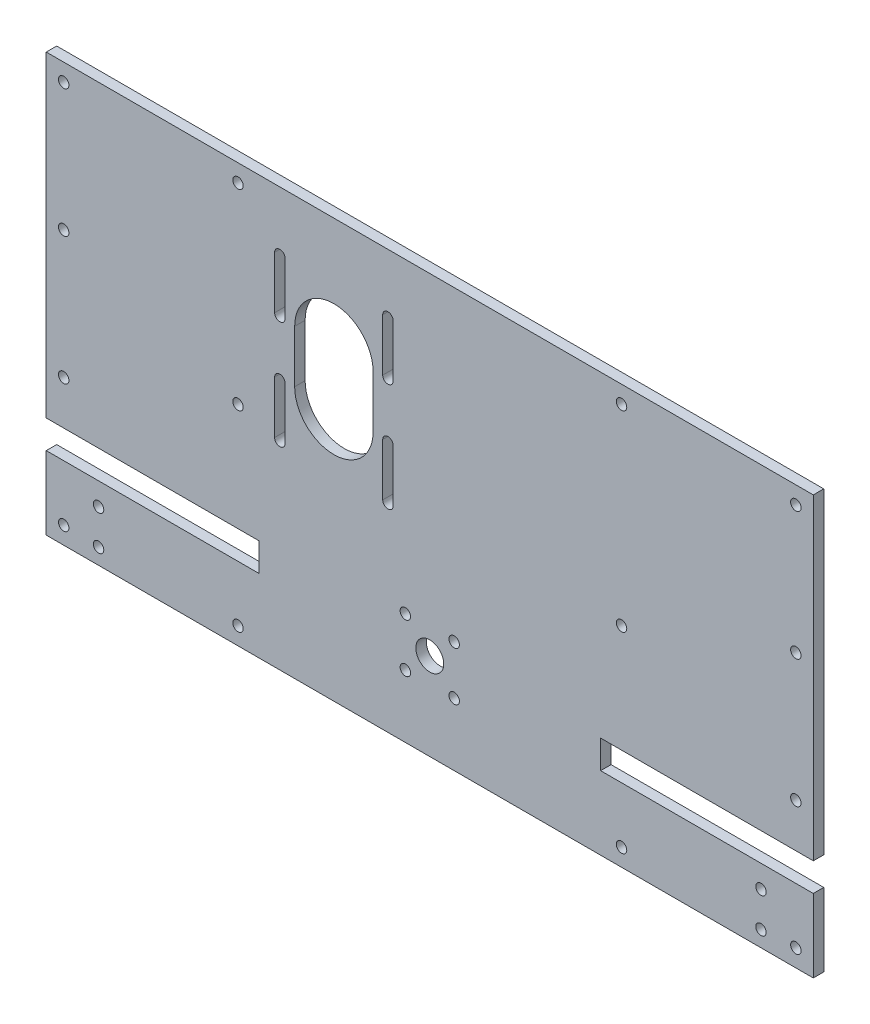
SolidWorks part; units mm, degrees
ref_plane "Plan de face" through (0, 0, 0) normal (0, 0, 1) x (1, 0, 0)
ref_plane "Plan de dessus" through (0, 0, 0) normal (0, 1, 0) x (1, 0, 0)
ref_plane "Plan de droite" through (0, 0, 0) normal (1, 0, 0) x (0, 0, -1)
sketch "Esquisse1" plane through (0, 0, 0) normal (0, 0, 1) x (1, 0, 0)
  line L0 (-27.5, 17.5) -> (-27.5, 32.5) construction
  line L1 (60, -65) -> (-60, -65)
  line L2 (60, -65) -> (60, -34)
  line L3 (60, 65) -> (-60, 65)
  line L4 (-60, -65) -> (-60, -34)
  line L5 (60, -65) -> (-60, 65) construction
  line L6 (60, 65) -> (-60, -65) construction
  line L9 (60, -55) -> (50, -55)
  line L10 (50, -65) -> (50, -55)
  line L13 (-60, -55) -> (-50, -55)
  line L14 (-50, -65) -> (-50, -55)
  line L15 (-38.75, 17.5) -> (-38.75, 32.5)
  line L16 (-16.25, 17.5) -> (-16.25, 32.5)
  line L17 (-43, 33) -> (-43, 48) construction
  line L18 (-44.5, 33) -> (-44.5, 48)
  line L19 (-41.5, 33) -> (-41.5, 48)
  line L20 (-43, 2) -> (-43, 17) construction
  line L21 (-44.5, 2) -> (-44.5, 17)
  line L22 (-41.5, 2) -> (-41.5, 17)
  line L23 (-27.5, 65) -> (-27.5, -65) construction
  line L24 (-27.5, 43.75) -> (-27.5, 6.25) construction
  line L27 (-12, 2) -> (-12, 17) construction
  line L30 (-10.5, 2) -> (-10.5, 17)
  line L31 (-13.5, 2) -> (-13.5, 17)
  line L32 (-12, 33) -> (-12, 48) construction
  line L33 (-10.5, 33) -> (-10.5, 48)
  line L34 (-13.5, 33) -> (-13.5, 48)
  line L35 (-105, -55) -> (-105, 65) construction
  line L36 (-60, -55) -> (-110, -55)
  line L37 (-60, -55) -> (-60, -34)
  line L38 (-60, 65) -> (-110, 65)
  line L39 (-110, -55) -> (-110, 65)
  line L40 (-60, -34) -> (-110, -34)
  line L42 (-60, -25.9) -> (-110, -25.9)
  line L43 (-110, -34) -> (-110, -25.9)
  line L44 (0, 65) -> (0, -65) construction
  line L45 (60, -25.9) -> (110, -25.9)
  line L46 (110, -34) -> (110, -25.9)
  line L47 (60, -34) -> (110, -34)
  line L49 (60, 65) -> (110, 65)
  line L50 (110, -55) -> (110, 65)
  line L51 (60, -55) -> (110, -55)
  line L52 (60, -55) -> (60, -34)
  line L54 (60, -34) -> (49, -34)
  line L55 (-60, -25.9) -> (-49, -25.9)
  line L57 (-60, -34) -> (-49, -34)
  line L58 (-49, -25.9) -> (-49, -34)
  line L59 (49, -25.9) -> (49, -34)
  line L60 (60, -25.9) -> (49, -25.9)
  line L62 (-60, -25.9) -> (-60, 65)
  line L63 (-60, -25.9) -> (-60, 65)
  line L64 (60, -25.9) -> (60, 65)
  line L65 (60, -25.9) -> (60, 65)
  arc A0 (-38.75, 17.5) -> (-16.25, 17.5) centre (-27.5, 17.5) ccw
  arc A1 (-16.25, 32.5) -> (-38.75, 32.5) centre (-27.5, 32.5) ccw
  arc A2 (-44.5, 33) -> (-41.5, 33) centre (-43, 33) ccw
  arc A3 (-41.5, 48) -> (-44.5, 48) centre (-43, 48) ccw
  arc A4 (-44.5, 2) -> (-41.5, 2) centre (-43, 2) ccw
  arc A5 (-41.5, 17) -> (-44.5, 17) centre (-43, 17) ccw
  arc A10 (-10.5, 2) -> (-13.5, 2) centre (-12, 2) cw
  arc A11 (-13.5, 17) -> (-10.5, 17) centre (-12, 17) cw
  arc A12 (-10.5, 33) -> (-13.5, 33) centre (-12, 33) cw
  arc A13 (-13.5, 48) -> (-10.5, 48) centre (-12, 48) cw
  circle A14 centre (-105, -50) radius 1.5
  circle A15 centre (-105, -13.3333) radius 1.5
  circle A16 centre (-105, 23.3333) radius 1.5
  circle A17 centre (-105, 60) radius 1.5
  circle A18 centre (105, -50) radius 1.5
  circle A19 centre (105, -13.3333) radius 1.5
  circle A20 centre (105, 23.3333) radius 1.5
  circle A21 centre (105, 60) radius 1.5
  circle A22 centre (-95, -40.4553) radius 1.5
  circle A26 centre (-95, -50.4553) radius 1.5
  circle A27 centre (95, -50.4553) radius 1.5
  circle A28 centre (95, -40.4553) radius 1.5
  point P0 (0, 0)
  point P14 (-27.5, 25)
  point P21 (-43, 40.5)
  point P28 (-43, 9.5)
  point P37 (-12, 9.5)
  point P44 (-12, 40.5)
  dimension "D13" = 90
  dimension "D17" = 3
  dimension "D22" = 3
  dimension "D23" = 3
  dimension "D1" = 10
  dimension "D2" = 10
  dimension "D3" = 130
  dimension "D4" = 120
  dimension "D5" = 32.5
  dimension "D6" = 15.5
  dimension "D7" = 22.5
  dimension "D8" = 3
  dimension "D9" = 15.5
  dimension "D10" = 15
  dimension "D11" = 3
  dimension "D12" = 31
  dimension "D14" = 8.1
  dimension "D15" = 21
  dimension "D16" = 5
  dimension "D18" = 5
  dimension "D19" = 5
  dimension "D20" = 50
  dimension "D24" = 11
  dimension "D21" = 4
extrude "Boss.-Extru.1" add sketch "Esquisse1" along normal blind 3 contours L14 L1 L10 L9 L2 L3 L4 L37 L13 A5 L22 A4 L21 A3 L19 A2 L18 A1 L16 A0 L15 L31 A11 L30 A10 L34 A13 L33 A12 | L42 L4 L38 L39 A17 A16 A15 | L45 L50 L49 L2 A20 A19 A21 | L2 L51 L50 L47 A18 | L4 L40 L39 L36 A14 region at (1.8169, -0.4375, 0) region at (84.7252, -44.4491, 0) region at (-84.7252, -44.4491, 0) region at (84.9062, 19.5323, 0) region at (-84.9062, 19.5323, 0)
sketch "Esquisse2" plane through (0, 0, 3) normal (0, 0, 1) x (1, 0, 0)
  line L0 (-55, 65) -> (-55, -55) construction
  line L1 (110, 65) -> (-110, 65) construction
  line L2 (110, -55) -> (50, -55) construction
  line L3 (50, -60) -> (-50, -60) construction
  line L4 (50, -65) -> (50, -55) construction
  line L5 (-50, -65) -> (-50, -55) construction
  line L6 (0, 65) -> (0, -65) construction
  line L7 (50, -65) -> (-50, -65) construction
  line L9 (-50, -65) -> (-50, -55) construction
  circle A0 centre (45, -60) radius 1.5
  circle A3 centre (-55, -50) radius 1.5
  circle A4 centre (-55, 5) radius 1.5
  circle A5 centre (-55, 60) radius 1.5
  circle A9 centre (22.5, -60) radius 1.5
  circle A10 centre (0, -60) radius 1.5
  circle A11 centre (-22.5, -60) radius 1.5
  circle A12 centre (-45, -60) radius 1.5
  circle A13 centre (55, -50) radius 1.5
  circle A14 centre (55, 5) radius 1.5
  circle A15 centre (55, 60) radius 1.5
  dimension "D2" = 3
  dimension "D6" = 3
  dimension "D1" = 5
  dimension "D3" = 5
  dimension "D5" = 5
  dimension "D7" = 5
  dimension "D4" = 5
  dimension "D8" = 3
extrude "Enlèv. mat.-Extru.2" cut sketch "Esquisse2" against normal blind 3
sketch "Esquisse3" plane through (0, 0, 3) normal (0, 0, 1) x (1, 0, 0)
  line L3 (50, -65) -> (-50, -65) construction
  line L4 (0, 65) -> (0, -65) construction
  line L5 (110, 65) -> (-110, 65) construction
  line L6 (-7, -23) -> (7, -23) construction
  line L7 (7, -42) -> (-7, -42) construction
  line L8 (12, -37) -> (12, -23) construction
  line L9 (7, -18) -> (-7, -18) construction
  line L10 (-12, -37) -> (-12, -23) construction
  line L11 (12, -42) -> (-12, -18) construction
  line L12 (12, -18) -> (-12, -42) construction
  line L13 (-7, -23) -> (-7, -37) construction
  circle A0 centre (0, -30) radius 4
  arc A2 (-7, -42) -> (-12, -37) centre (-7, -37) cw construction
  arc A3 (7, -42) -> (12, -37) centre (7, -37) ccw construction
  arc A4 (12, -23) -> (7, -18) centre (7, -23) ccw construction
  arc A5 (-7, -18) -> (-12, -23) centre (-7, -23) ccw construction
  circle A6 centre (-7, -23) radius 1.5
  circle A7 centre (7, -23) radius 1.5
  circle A8 centre (7, -37) radius 1.5
  circle A9 centre (-7, -37) radius 1.5
  dimension "D1" = 8
  dimension "D2" = 35
  dimension "D3" = 14
  dimension "D4" = 5
  dimension "D5" = 3
  dimension "D8" = 14
  dimension "D6" = 2
  dimension "D7" = 2
extrude "Enlèv. mat.-Extru.3" cut sketch "Esquisse3" against normal blind 10
sketch "Esquisse4" plane through (0, 0, 3) normal (0, 0, 1) x (1, 0, 0)
  line L0 (-50, -55) -> (50, -55)
  line L1 (50, -55) -> (50, -76.4572)
  line L2 (50, -76.4572) -> (-50, -76.4572)
  line L3 (-50, -76.4572) -> (-50, -55)
extrude "Enlèv. mat.-Extru.4" cut sketch "Esquisse4" against normal blind 10
